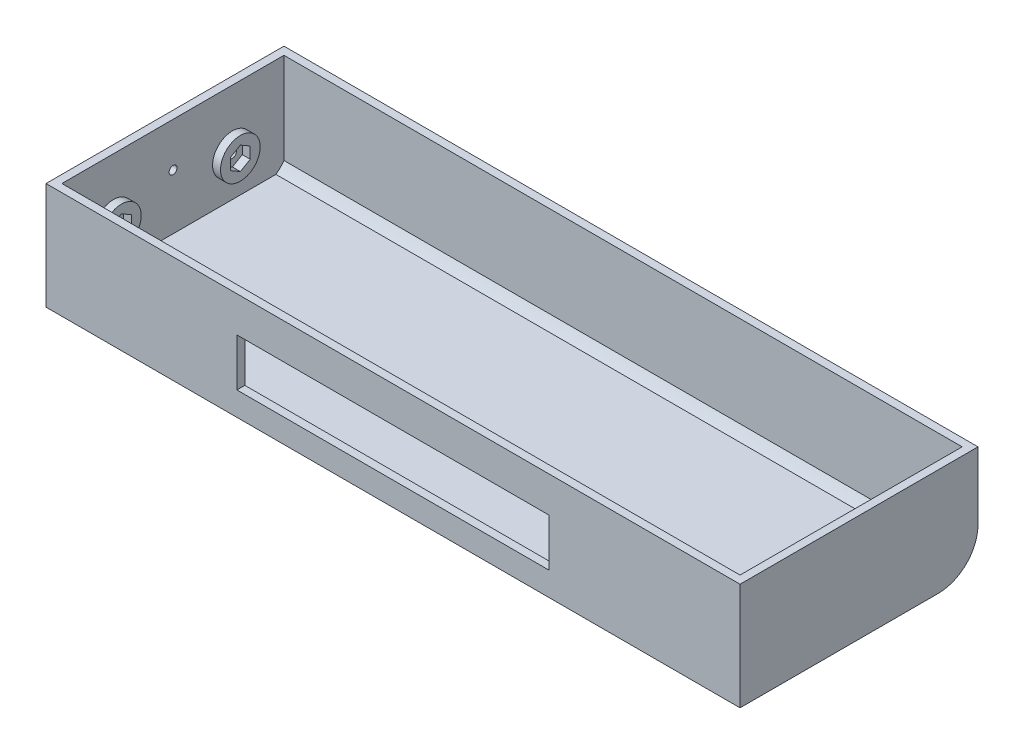
SolidWorks part; units mm, degrees
note: The reader was unsure of these and kept them because the rebuilt part matched: shared geometry of "Sketch1<2>", "Sketch5<4>", "Sketch9<3>", "Sketch11<3>".
material "ABS PC"
ref_plane "Front Plane" through (0, 0, 0) normal (0, 0, 1) x (1, 0, 0)
ref_plane "Top Plane" through (0, 0, 0) normal (0, 1, 0) x (1, 0, 0)
ref_plane "Right Plane" through (0, 0, 0) normal (1, 0, 0) x (0, 0, -1)
sketch "Sketch1" plane through (0, 0, 0) normal (0, 1, 0) x (1, 0, 0)
  line L0 (-85.5, 25.1257) -> (85.5, 25.1257)
  line L1 (-87.5, -32.8743) -> (87.5, -32.8743)
  line L2 (-87.5, -32.8743) -> (-87.5, 27.1257)
  line L3 (-87.5, 27.1257) -> (87.5, 27.1257)
  line L4 (87.5, -32.8743) -> (87.5, 27.1257)
  line L5 (-87.5, -32.8743) -> (87.5, 27.1257) construction
  line L6 (-87.5, 27.1257) -> (87.5, -32.8743) construction
  line L7 (85.5, -30.8743) -> (85.5, 25.1257)
  line L8 (-85.5, -30.8743) -> (85.5, -30.8743)
  line L9 (-85.5, -30.8743) -> (-85.5, 25.1257)
  point P0 (0, 0)
  dimension "D1" = 175
  dimension "D2" = 60
  dimension "D3" = 2
extrude "Boss-Extrude1" add sketch "Sketch1" along normal blind 25
extrude "Boss-Extrude2" add sketch "Sketch1<2>" against normal blind 2 contours L1 L4 L3 L2
sketch "Sketch1<2>" plane through (0, 0, 0) normal (0, 1, 0) x (1, 0, 0) same geometry as "Sketch1"
sketch "Sketch2" plane through (-87.5, 0, 0) normal (-1, 0, 0) x (0, 0, 1)
  line L0 (2.8743, 20.0545) -> (2.8743, 0.0545) construction
  line L1 (-27.1257, 10) -> (32.8743, 10) construction
  line L2 (-27.1257, 25) -> (-27.1257, -2) construction
  line L3 (-13.6257, 8.5) -> (-10.6257, 8.5)
  line L4 (-13.6257, 8.5) -> (-13.6257, 11.5)
  line L5 (-13.6257, 11.5) -> (-10.6257, 11.5)
  line L6 (-10.6257, 8.5) -> (-10.6257, 11.5)
  line L7 (-13.6257, 8.5) -> (-10.6257, 11.5) construction
  line L8 (-13.6257, 11.5) -> (-10.6257, 8.5) construction
  line L9 (19.3743, 11.5) -> (16.3743, 8.5) construction
  line L10 (19.3743, 8.5) -> (16.3743, 11.5) construction
  line L11 (16.3743, 8.5) -> (16.3743, 11.5)
  line L12 (19.3743, 11.5) -> (16.3743, 11.5)
  line L13 (19.3743, 8.5) -> (19.3743, 11.5)
  line L14 (19.3743, 8.5) -> (16.3743, 8.5)
  circle A0 centre (-12.1257, 10) radius 9.5 construction
  point P4 (-12.1257, 10)
  point P6 (2.8743, 10.0545)
  point P8 (-12.1257, 10)
  point P18 (17.8743, 10)
  dimension "D1" = 3
  dimension "D3" = 13.5
  dimension "D5" = 19
  dimension "D2" = 3
  dimension "D4" = 13.5
sketch "Sketch3" plane through (0, 0, 32.8743) normal (0, 0, 1) x (1, 0, 0)
  line L1 (-39.3652, 3.9899) -> (39.3652, 3.9899)
  line L2 (-39.3652, 3.9899) -> (-39.3652, 16.0101)
  line L3 (-39.3652, 16.0101) -> (39.3652, 16.0101)
  line L4 (39.3652, 3.9899) -> (39.3652, 16.0101)
  line L5 (-39.3652, 3.9899) -> (39.3652, 16.0101) construction
  line L6 (-39.3652, 16.0101) -> (39.3652, 3.9899) construction
  point P0 (0, 10)
extrude "Cut-Extrude2" cut sketch "Sketch3" against normal up to surface (2 mm away) up to face at (0, 12.5, 30.8743)
sketch "Sketch5" plane through (85.5, 0, 0) normal (-1, 0, 0) x (0, 0, 1)
  line L0 (30.8743, 2) -> (30.8743, 20)
  line L1 (30.8743, 2) -> (-25.1257, 2)
  line L2 (2.8743, 2) -> (2.8743, 20)
  line L3 (30.8743, 20) -> (-25.1257, 20)
  line L4 (-25.1257, 2) -> (-25.1257, 20)
  line L5 (2.8743, 2) -> (-25.1257, 20) construction
  line L6 (2.8743, 20) -> (-25.1257, 2) construction
  circle A0 centre (17.8743, 10) radius 5
  circle A1 centre (-12.1257, 10) radius 5
  point P0 (-12.1257, 10)
extrude "Boss-Extrude3" add sketch "Sketch5" along normal blind 2
extrude "Boss-Extrude4" add sketch "Sketch5<4>" along normal blind 6 separate body
sketch "Sketch5<4>" plane through (85.5, 0, 0) normal (-1, 0, 0) x (0, 0, 1) same geometry as "Sketch5"
sketch "Sketch6" plane through (79.5, 0, 0) normal (-1, 0, 0) x (0, 0, 1)
  line L1 (-13.6257, 8.5) -> (-10.6257, 8.5)
  line L2 (-13.6257, 8.5) -> (-13.6257, 11.5)
  line L3 (-13.6257, 11.5) -> (-10.6257, 11.5)
  line L4 (-10.6257, 8.5) -> (-10.6257, 11.5)
  line L5 (-13.6257, 8.5) -> (-10.6257, 11.5) construction
  line L6 (-13.6257, 11.5) -> (-10.6257, 8.5) construction
  point P0 (-12.1257, 10)
sketch "Sketch7" plane through (79.5, 0, 0) normal (-1, 0, 0) x (0, 0, 1)
  line L1 (16.3743, 8.5) -> (19.3743, 8.5)
  line L2 (16.3743, 8.5) -> (16.3743, 11.5)
  line L3 (16.3743, 11.5) -> (19.3743, 11.5)
  line L4 (19.3743, 8.5) -> (19.3743, 11.5)
  line L5 (16.3743, 8.5) -> (19.3743, 11.5) construction
  line L6 (16.3743, 11.5) -> (19.3743, 8.5) construction
  point P0 (17.8743, 10)
sketch "Sketch8" plane through (-87.5, 0, 0) normal (-1, 0, 0) x (0, 0, 1)
  line L1 (-12.1257, 12.8868) -> (-14.6257, 11.4434)
  line L2 (-14.6257, 11.4434) -> (-14.6257, 8.5566)
  line L3 (-14.6257, 8.5566) -> (-12.1257, 7.1132)
  line L4 (-12.1257, 7.1132) -> (-9.6257, 8.5566)
  line L5 (-9.6257, 8.5566) -> (-9.6257, 11.4434)
  line L6 (-9.6257, 11.4434) -> (-12.1257, 12.8868)
  line L7 (-14.6257, 11.4434) -> (-14.6257, 8.5566)
  line L8 (-14.6257, 8.5566) -> (-12.1257, 7.1132)
  line L9 (-12.1257, 7.1132) -> (-9.6257, 8.5566)
  line L10 (-9.6257, 8.5566) -> (-9.6257, 11.4434)
  line L11 (-9.6257, 11.4434) -> (-12.1257, 12.8868)
  line L12 (-12.1257, 12.8868) -> (-14.6257, 11.4434)
  circle A0 centre (-12.1257, 10) radius 5
  circle A1 centre (-12.1257, 10) radius 2.5 construction
  circle A2 centre (-12.1257, 10) radius 1.5
  circle A3 centre (-12.1257, 10) radius 1
  circle A4 centre (-12.1257, 10) radius 2.5 construction
ref_plane "Plane1" through (0, 0, 2.8743) normal (0, 0, 1) x (1, 0, 0)
sketch3d "3DSketch1"
  line L0 (-87.5, 10, -12.1257) -> (83.5, 10, -12.1257) construction
  line L1 (-85.5, 0, 2.8743) -> (83.5, 2, 2.8743)
sketch "Sketch9" plane through (79.5, 0, 0) normal (-1, 0, 0) x (0, 0, 1)
  circle A0 centre (-12.1257, 10) radius 3
extrude "Cut-Extrude3" cut sketch "Sketch9" against normal blind 2
extrude "Boss-Extrude5" add sketch "Sketch9<3>" against normal blind 2 separate body
sketch "Sketch9<3>" plane through (79.5, 0, 0) normal (-1, 0, 0) x (0, 0, 1) same geometry as "Sketch9"
extrude "Cut-Extrude4" cut sketch "Sketch6" against normal blind 2
extrude "Cut-Extrude5" cut sketch "Sketch8" against normal blind 2 contours A3
sketch "Sketch10" plane through (-85.5, 0, 0) normal (1, 0, 0) x (0, 0, -1)
  line L1 (12.1257, 12.8868) -> (9.6257, 11.4434)
  line L2 (9.6257, 11.4434) -> (9.6257, 8.5566)
  line L3 (9.6257, 8.5566) -> (12.1257, 7.1132)
  line L4 (12.1257, 7.1132) -> (14.6257, 8.5566)
  line L5 (14.6257, 8.5566) -> (14.6257, 11.4434)
  line L6 (14.6257, 11.4434) -> (12.1257, 12.8868)
  circle A0 centre (12.1257, 10) radius 2.5 construction
  circle A1 centre (12.1257, 10) radius 5
extrude "Boss-Extrude8" add sketch "Sketch10" along normal blind 2
mirror "Mirror1" about plane through (0, 0, 2.8743) normal (0, 0, 1) of "Cut-Extrude5", "Boss-Extrude8"
sketch "Sketch11" plane through (79.5, 0, 0) normal (-1, 0, 0) x (0, 0, 1)
  line L1 (16.3743, 8.5) -> (19.3743, 8.5)
  line L2 (16.3743, 8.5) -> (16.3743, 11.5)
  line L3 (16.3743, 11.5) -> (19.3743, 11.5)
  line L4 (19.3743, 8.5) -> (19.3743, 11.5)
  line L5 (16.3743, 8.5) -> (19.3743, 11.5) construction
  line L6 (16.3743, 11.5) -> (19.3743, 8.5) construction
  circle A0 centre (17.8743, 10) radius 3
extrude "Cut-Extrude6" cut sketch "Sketch11" against normal blind 2 contours L1 L4 L3 L2 | A0 L4 L1 L2 L3
extrude "Boss-Extrude9" add sketch "Sketch11<3>" against normal blind 2 separate body
sketch "Sketch11<3>" plane through (79.5, 0, 0) normal (-1, 0, 0) x (0, 0, 1) same geometry as "Sketch11"
sketch "Sketch12" plane through (-87.5, 0, 0) normal (-1, 0, 0) x (0, 0, 1)
  circle A0 centre (2.8323, 13.914) radius 1
extrude "Cut-Extrude7" cut sketch "Sketch12" against normal up to surface (2 mm away) up to face at (-85.5, 10, 12.8743)
sketch "Sketch13" plane through (-87.5, 0, 0) normal (-1, 0, 0) x (0, 0, 1)
  circle A0 centre (-27.488, 9.5726) radius 1
extrude "Boss-Extrude10" add sketch "Sketch13" along normal mid plane 10
sketch "Sketch14" plane through (-92.5, 0, 0) normal (-1, 0, 0) x (0, 0, 1)
  circle A0 centre (-27.488, 9.5726) radius 2
  circle A1 centre (-27.488, 9.5726) radius 3
  dimension "D1" = 4
  dimension "D2" = 1
extrude "Boss-Extrude11" add sketch "Sketch14" along normal mid plane 9 separate body
fillet "Fillet1" radius 10 1 edges at (0, -2, -27.1257)
sketch "Sketch15" plane through (-87.5, 0, 0) normal (-1, 0, 0) x (0, 0, 1)
  circle A0 centre (-12.1257, 10) radius 1
  circle A1 centre (2.8323, 13.914) radius 1
  circle A2 centre (17.8743, 10) radius 1
extrude "Boss-Extrude12" add sketch "Sketch15" along normal blind 10 separate body
sketch "Sketch16" plane through (0, -8.781, -16.5805) normal (0, 0.468, 0.8837) x (1, 0, 0)
  line L0 (-97, 24.3244) -> (-97, 18.3244) construction
  circle A0 centre (-95.5, 21.3244) radius 1
  dimension "D1" = 1.5
extrude "Cut-Extrude9" cut sketch "Sketch16" along normal blind 3
